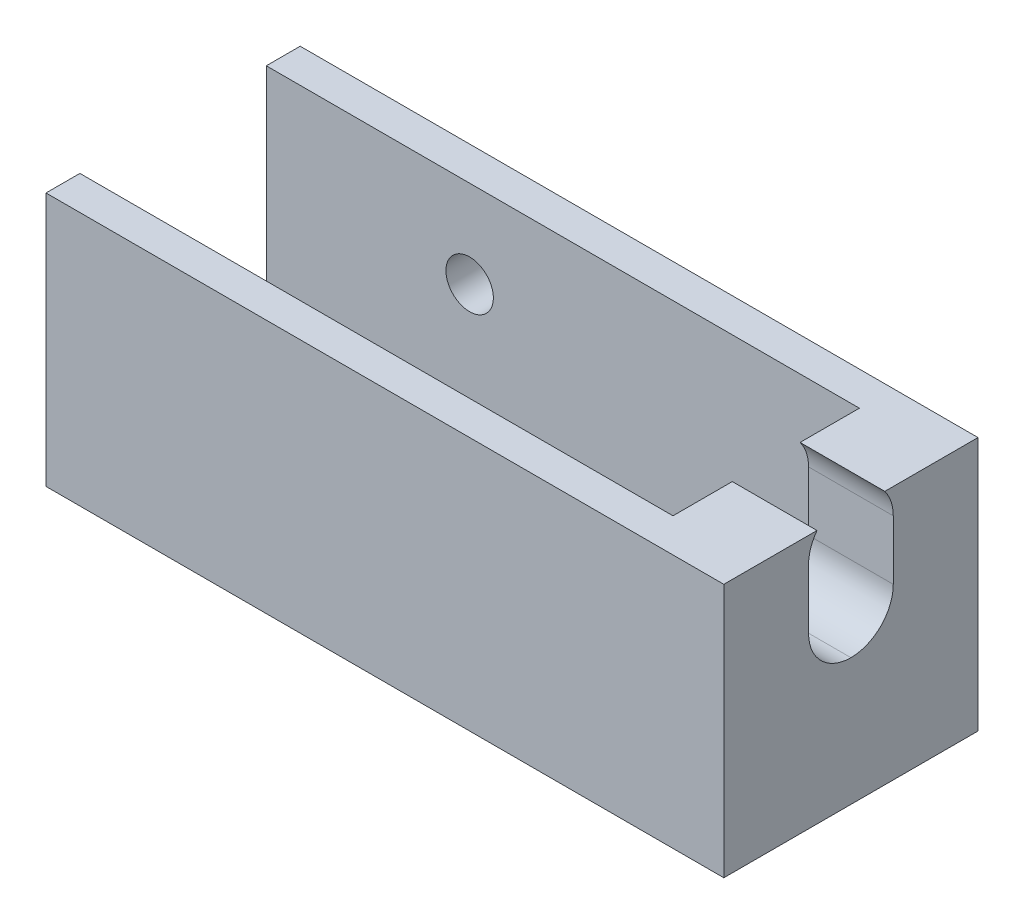
SolidWorks part; units mm, degrees
ref_plane "Front Plane" through (0, 0, 0) normal (0, 0, 1) x (1, 0, 0)
ref_plane "Top Plane" through (0, 0, 0) normal (0, 1, 0) x (1, 0, 0)
ref_plane "Right Plane" through (0, 0, 0) normal (1, 0, 0) x (0, 0, -1)
sketch "Sketch1" plane through (0, 0, 0) normal (0, 1, 0) x (1, 0, 0)
  line L1 (-20, -7.5) -> (20, -7.5)
  line L2 (-20, -7.5) -> (-20, 7.5)
  line L3 (-20, 7.5) -> (20, 7.5)
  line L4 (20, -7.5) -> (20, 7.5)
  line L5 (-20, -7.5) -> (20, 7.5) construction
  line L6 (-20, 7.5) -> (20, -7.5) construction
  point P0 (0, 0)
  dimension "D1" = 40
  dimension "D2" = 15
extrude "Boss-Extrude1" add sketch "Sketch1" along normal blind 15
ref_plane "Plane1" through (20, 0, 0) normal (1, 0, 0) x (0, 0, -1)
sketch "Sketch2" plane through (20, 0, 0) normal (1, 0, 0) x (0, 0, -1)
  line L0 (-2.5, 13.5) -> (-2.5, 7.5)
  line L1 (-7.5, 15) -> (7.5, 15) construction
  line L2 (0, 15) -> (0, 13.5) construction
  line L3 (-2.5, 7.5) -> (2.5, 7.5)
  line L4 (2.5, 7.5) -> (2.5, 13.5)
  arc A0 (2.5, 13.5) -> (-2.5, 13.5) centre (0, 13.5) ccw
  dimension "D1" = 5
  dimension "D2" = 1.5
  dimension "D3" = 6
extrude "Cut-Extrude1" cut sketch "Sketch2" against normal blind 5
ref_plane "Plane2" through (0, 15, 0) normal (0, 1, 0) x (1, 0, 0)
sketch "Sketch3" plane through (0, 15, 0) normal (0, 1, 0) x (1, 0, 0)
  line L0 (-18, 5.5) -> (-20, 5.5)
  line L2 (-18, 5.5) -> (-18, 7.5) construction
  line L3 (20, 7.5) -> (-20, 7.5) construction
  line L4 (15, 2) -> (15, 5.5)
  line L5 (15, 5.5) -> (-18, 5.5)
  line L7 (-18, -5.5) -> (15, -5.5)
  line L8 (15, -5.5) -> (15, 2)
  line L9 (-20, 7.5) -> (-20, -7.5) construction
  line L10 (-20, 5.5) -> (-20, -5.5)
  line L11 (-20, -5.5) -> (-18, -5.5)
  dimension "D2" = 2
  dimension "D3" = 11
extrude "Cut-Extrude2" cut sketch "Sketch3" against normal blind 13
fillet "Fillet3" radius 2.5 1 edges at (17.5, 7.5, -2.5) type face fillet first side face at (17.5, 10.5, -2.5) second side face at (17.5, 7.5, 0)
fillet "Fillet4" radius 2.5 1 edges at (17.5, 7.5, 2.5) type face fillet first side face at (17.5, 10.5, 2.5) second side face at (17.5, 7.5, 1.25)
extrude "Cut-Extrude3" cut sketch "Sketch4" against normal blind 8
sketch "Sketch4" plane through (-14.63, 3.5417, -7.5) normal (0, 0, -1) x (-1, 0, 0)
  circle A0 centre (-6.63, 6.2898) radius 1.4
ref_plane "Plane3" through (0, 2, 0) normal (0, 1, 0) x (1, 0, 0)
sketch "Sketch5" plane through (0, 2, 0) normal (0, 1, 0) x (1, 0, 0)
  circle A0 centre (-15.9327, 0) radius 1
  dimension "D1" = 2
extrude "Cut-Extrude4" cut sketch "Sketch5" against normal blind 10
